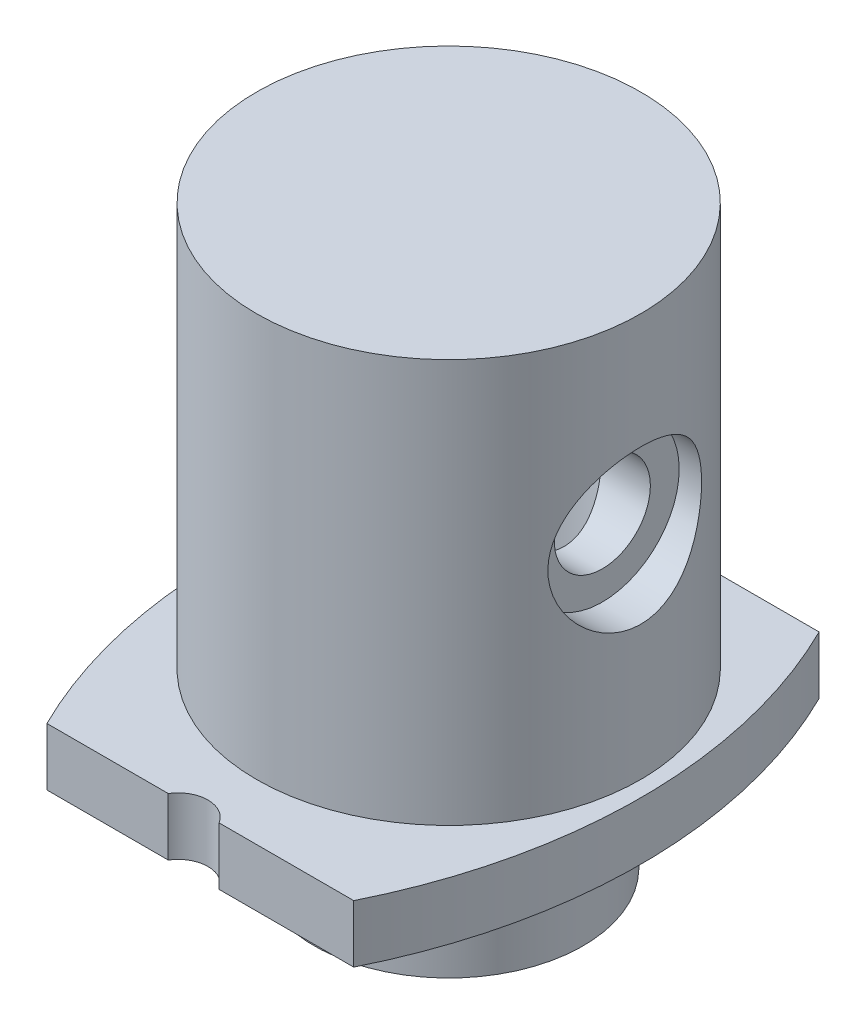
SolidWorks part; units mm, degrees
ref_plane "Front Plane" through (0, 0, 0) normal (0, 0, 1) x (1, 0, 0)
ref_plane "Top Plane" through (0, 0, 0) normal (0, 1, 0) x (1, 0, 0)
ref_plane "Right Plane" through (0, 0, 0) normal (1, 0, 0) x (0, 0, -1)
sketch "Sketch1" plane through (0, 0, 0) normal (0, 1, 0) x (1, 0, 0)
  circle A0 centre (0, 0) radius 10
  dimension "D1" = 20
extrude "Boss-Extrude1" add sketch "Sketch1" along normal blind 21
sketch "Sketch2" plane through (0, 0, 0) normal (0, -1, 0) x (1, 0, 0)
  line L1 (0, 0) -> (0, -14.3614) construction
  line L2 (-7.9858, 12.9282) -> (7.9858, 12.9282)
  line L3 (-7.9858, -11.2976) -> (7.9858, -11.2976)
  arc A1 (-7.9858, 12.9282) -> (-7.9858, -11.2976) centre (16.4464, 0.8153) ccw
  arc A3 (7.9858, 12.9282) -> (7.9858, -11.2976) centre (-16.4464, 0.8153) cw
extrude "Boss-Extrude2" add sketch "Sketch2" along normal blind 3 contours L3 A3 L2 A1
sketch "Sketch3" plane through (0, -3, 0) normal (0, -1, 0) x (1, 0, 0)
  circle A0 centre (0, 0) radius 7
  dimension "D1" = 14
extrude "Boss-Extrude3" add sketch "Sketch3" along normal blind 6
sketch "Sketch4" plane through (0, -9, 0) normal (0, -1, 0) x (1, 0, 0)
  circle A0 centre (0, 0) radius 6
  dimension "D1" = 12
extrude "Cut-Extrude1" cut sketch "Sketch4" against normal blind 25
ref_plane "Plane1" through (10, 0, 0) normal (1, 0, 0) x (0, 0, -1)
sketch "Sketch5" plane through (10, 0, 0) normal (1, 0, 0) x (0, 0, -1)
  line L0 (-7, -9) -> (7, -9) construction
  circle A0 centre (0, 11) radius 4
  circle A1 centre (0, 11) radius 2.5
  dimension "D1" = 8
  dimension "D2" = 5
  dimension "D3" = 20
extrude "Cut-Extrude2" cut sketch "Sketch5" against normal blind 2 contours A0
extrude "Cut-Extrude3" cut sketch "Sketch5<3>" against normal up to next contours A1 region at (10, 11, 0)
sketch "Sketch5<3>" plane through (10, 0, 0) normal (1, 0, 0) x (0, 0, -1) same geometry as "Sketch5"
sketch "Sketch6" plane through (0, 0, 0) normal (0, 1, 0) x (1, 0, 0)
  circle A0 centre (0.3963, 13.7004) radius 1.55
  circle A1 centre (-0.3463, -13.736) radius 1.55
  dimension "D1" = 3.1
  dimension "D2" = 3.1
extrude "Cut-Extrude4" cut sketch "Sketch6" against normal through all
